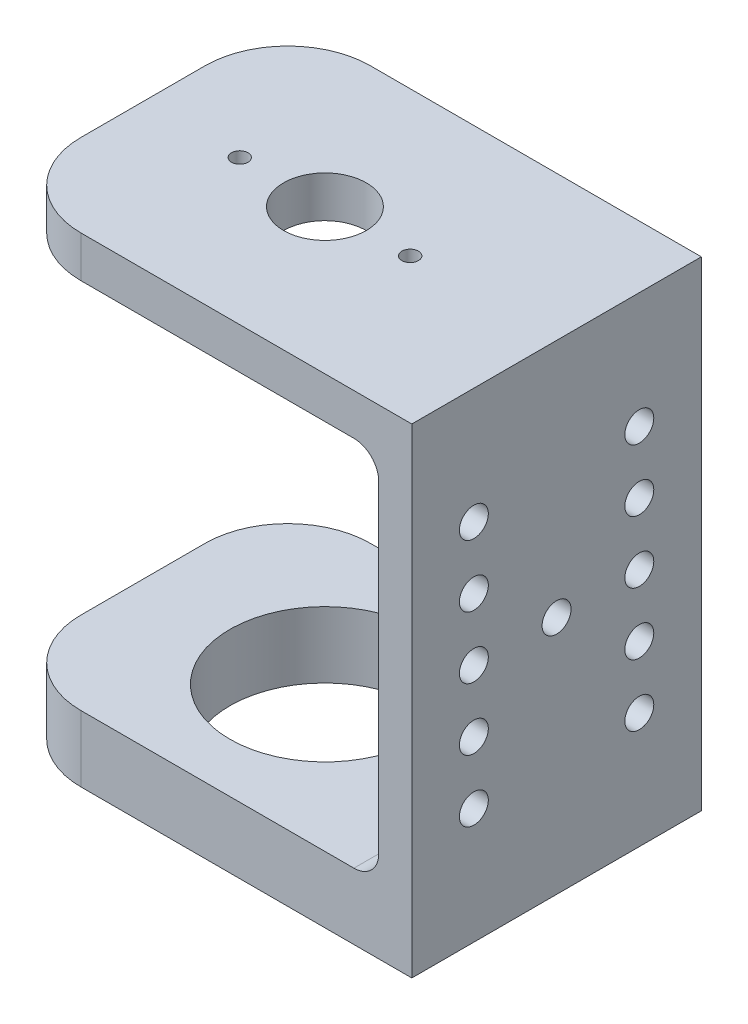
SolidWorks part; units mm, degrees
ref_plane "Front Plane" through (0, 0, 0) normal (0, 0, 1) x (1, 0, 0)
ref_plane "Top Plane" through (0, 0, 0) normal (0, 1, 0) x (1, 0, 0)
ref_plane "Right Plane" through (0, 0, 0) normal (1, 0, 0) x (0, 0, -1)
sketch "Sketch1" plane through (0, 0, 0) normal (0, 1, 0) x (1, 0, 0)
  line L1 (28, 17.5) -> (-22, 17.5)
  line L2 (28, 17.5) -> (28, -17.5)
  line L3 (28, -17.5) -> (-22, -17.5)
  line L4 (-22, 17.5) -> (-22, -17.5)
  circle A0 centre (0, 0) radius 11.5
  point P8 (28, 0)
  dimension "D1" = 23
  dimension "D2" = 35
  dimension "D3" = 50
  dimension "D4" = 28
extrude "Boss-Extrude1" add sketch "Sketch1" along normal blind 8
sketch "Sketch2" plane through (0, 8, 0) normal (0, 1, 0) x (1, 0, 0)
  line L0 (-22, -17.5) -> (28, -17.5) construction
  line L1 (28, 17.5) -> (24, 17.5)
  line L2 (28, 17.5) -> (28, -17.5)
  line L3 (28, -17.5) -> (24, -17.5)
  line L4 (24, 17.5) -> (24, -17.5)
  dimension "D1" = 4
extrude "Boss-Extrude2" add sketch "Sketch2" along normal blind 45
sketch "Sketch3" plane through (0, 53, 0) normal (0, 1, 0) x (1, 0, 0)
  line L1 (-22, 17.5) -> (28, 17.5)
  line L2 (-22, 17.5) -> (-22, -17.5)
  line L3 (-22, -17.5) -> (28, -17.5)
  line L4 (28, 17.5) -> (28, -17.5)
  circle A0 centre (0, 0) radius 5
  circle A1 centre (10.3, 0) radius 1
  circle A2 centre (-10.3, 0) radius 1
  dimension "D1" = 10
  dimension "D4" = 2
  dimension "D5" = 2
  dimension "D2" = 10.3
  dimension "D3" = 10.3
extrude "Boss-Extrude3" add sketch "Sketch3" along normal blind 5
fillet "Fillet1" radius 10 4 edges at (-22, 55.5, 17.5) (-22, 55.5, -17.5) (-22, 4, -17.5) (-22, 4, 17.5)
fillet "Fillet2" radius 3 2 edges at (24, 53, 0) (24, 8, 0)
sketch "Sketch4" plane through (28, 0, 0) normal (1, 0, 0) x (0, 0, -1)
  line L2 (-17.5, 58) -> (17.5, 58) construction
  circle A2 centre (0, 29) radius 1.75
  circle A3 centre (-10, 36.5) radius 1.75
  circle A5 centre (0, 29) radius 1.75
  circle A6 centre (10, 21.5) radius 1.75
  circle A7 centre (0, 29) radius 1.75
  circle A9 centre (0, 29) radius 1.75
  circle A10 centre (-10, 44) radius 1.75
  circle A11 centre (-10, 14) radius 1.75
  circle A12 centre (10, 14) radius 1.75
  circle A14 centre (-10, 29) radius 1.75
  circle A15 centre (10, 29) radius 1.75
  circle A16 centre (-10, 21.5) radius 1.75
  circle A17 centre (7.5, 39) radius 1.75 [skipped]
  circle A18 centre (-7.5, 19) radius 1.75 [skipped]
  circle A19 centre (10, 36.5) radius 1.75
  circle A20 centre (10, 44) radius 1.75
  point P18 (0, 0)
  point P20 (0, 29)
  point P23 (0, 0)
  point P29 (0, 0)
  point P30 (0, 0)
  point P31 (0, 0)
  point P32 (10, 36.5)
  point P33 (10, 44)
  dimension "D1" = 3.5
  dimension "D3" = 7.5
  dimension "D4" = 10
  dimension "D7" = 7.5
  dimension "D8" = 29
  dimension "D10" = 7.5
  dimension "D5" = 4
extrude "Cut-Extrude1" cut sketch "Sketch4" against normal through all contours A10 | A3 | A2 | A11 | A6 | A12 | A16 | A14 | A15 | A19 | A20 | A14 | A16 | A19 region at (28, 29, 0) region at (28, 36.5, 10) region at (28, 21.5, -10) region at (28, 44, 10) region at (28, 14, 10) region at (28, 14, -10) region at (28, 29, 10) region at (28, 29, -10) region at (28, 21.5, 10) region at (28, 36.5, -10) region at (28, 44, -10)
